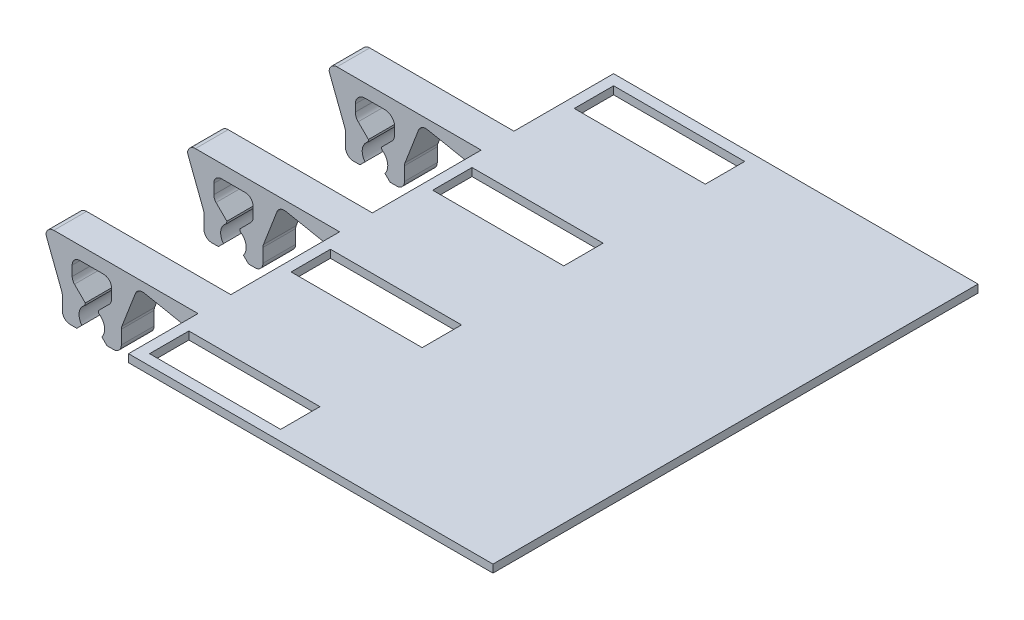
SolidWorks part; units mm, degrees
ref_plane "Front Plane" through (0, 0, 0) normal (0, 0, 1) x (1, 0, 0)
ref_plane "Top Plane" through (0, 0, 0) normal (0, 1, 0) x (1, 0, 0)
ref_plane "Right Plane" through (0, 0, 0) normal (1, 0, 0) x (0, 0, -1)
sketch "Sketch1" plane through (0, 0, 0) normal (0, 1, 0) x (1, 0, 0)
  line L1 (-27.8, -37) -> (27.8, -37)
  line L2 (-27.8, -37) -> (-27.8, 37)
  line L3 (-27.8, 37) -> (27.8, 37)
  line L4 (27.8, -37) -> (27.8, 37)
  line L5 (-27.8, -37) -> (27.8, 37) construction
  line L6 (-27.8, 37) -> (27.8, -37) construction
  point P0 (0, 0)
  dimension "D1" = 55.6
  dimension "D2" = 74
extrude "plate" add sketch "Sketch1" along normal blind 1.2
sketch "Sketch5" plane through (0, 1.2, 0) normal (0, 1, 0) x (1, 0, 0)
  line L1 (-26.2, 29.4) -> (-6.2, 29.4)
  line L2 (-26.2, 29.4) -> (-26.2, 35.4)
  line L3 (-26.2, 35.4) -> (-6.2, 35.4)
  line L4 (-6.2, 29.4) -> (-6.2, 35.4)
  line L5 (-27.8, 37) -> (-27.8, -37) construction
  line L7 (27.8, 37) -> (-27.8, 37) construction
  dimension "D1" = 20
  dimension "D2" = 6
  dimension "D3" = 1.6
  dimension "D4" = 1.6
extrude "air window" cut sketch "Sketch5" against normal blind 1.6
pattern_linear "windows" count 4 spacing 21.6 along (0, 0, 1) of "air window"
ref_plane "slot end 1" through (0, 0, -29.4) normal (0, 0, -1) x (-1, 0, 0)
ref_plane "slot start 2" through (0, 0, -13.8) normal (0, 0, 1) x (1, 0, 0)
ref_plane "Plane3" through (0, 0, -16.8) normal (0, 0, 1) x (1, 0, 0)
ref_plane "rod plane" through (0, -8, 0) normal (0, -1, 0) x (-1, 0, 0)
ref_axis "front rod" through (-44, -8, -44.0643) along (0, 0, -1)
ref_axis "back rod" through (14, -8, -40.7) along (0, 0, 1)
sketch "Sketch9" plane through (0, -8, 0) normal (0, -1, 0) x (-1, 0, 0)
  line L0 (44, 0) -> (-14, 0) construction
  line L1 (44, 44.0643) -> (44, 157.3237) construction
  line L2 (-14, 40.7) -> (-14, -40.7) construction
  point P9 (15, 0)
ref_plane "mid rods" through (-15, -8, 0) normal (1, 0, 0) x (0, 0, -1)
sketch "Sketch6" plane through (0, 0, -16.8) normal (0, 0, 1) x (1, 0, 0)
  line L5 (-37, 0) -> (-39.5, -6.5)
  line L7 (9.5, -6.5) -> (-39.5, -6.5) construction
  line L10 (14, -1.4409) -> (14, 65.3362) construction
  line L11 (14, -10) -> (14, 0) construction
  line L12 (-27.8, 0) -> (27.8, 0) construction
  line L13 (-48.5, -10) -> (-39.5, -10)
  line L14 (-44, -10.0897) -> (-44, 1.2) construction
  line L16 (-44, -94.8555) -> (-44, -30.3764) construction
  line L17 (7, 0) -> (21, 0)
  line L19 (-51, 1.2) -> (-27.8, 1.2)
  line L23 (-27.8, 1.2) -> (-18.6, 1.2)
  line L24 (-18.6, 1.2) -> (-18.6, 0)
  line L25 (-18.6, 0) -> (-27.8, -1.8)
  line L26 (-27.8, -1.8) -> (-37, 0)
  line L27 (-27.8, -1.8) -> (-27.8, 1.2) construction
  line L28 (-6.2, 0) -> (-26.2, 0) construction
  line L29 (-39.5, -6.5) -> (-39.5, -10)
  line L30 (-48.5, -6.5) -> (-48.5, -10)
  line L31 (-51, 0) -> (-48.5, -6.5)
  line L32 (-51, 1.2) -> (-51, 0)
  line L34 (21, 0) -> (18.5, -6.5)
  line L35 (18.5, -6.5) -> (18.5, -10)
  line L36 (9.5, -6.5) -> (9.5, -10)
  line L37 (18.5, -10) -> (9.5, -10)
  line L38 (7, 0) -> (9.5, -6.5)
  line L40 (-26.2, 1.2) -> (-6.2, 1.2) construction
  line L41 (-27.8, 1.2) -> (-27.8, 0) construction
  point P9 (14, -10)
  point P23 (-44, -4.4448)
  dimension "D2" = 3
  dimension "D3" = 10
  dimension "D4" = 9
  dimension "D5" = 3.5
  dimension "D6" = 2.5
extrude "clips" add sketch "Sketch6" against normal blind 5
sketch "Sketch7" plane through (0, 0, -16.8) normal (0, 0, 1) x (1, 0, 0)
  line L0 (-45.5, -10) -> (-42.5, -10)
  line L1 (-48.5, -10) -> (-39.5, -10) construction
  line L2 (-45.5, -10) -> (-45, -6)
  line L3 (-45, -6) -> (-47, -4)
  line L6 (-41, -0.8) -> (-41, -4)
  line L7 (-41, -4) -> (-43, -6)
  line L8 (-43, -6) -> (-42.5, -10)
  line L9 (-44.9448, 0) -> (24.1674, 0) construction
  line L10 (14, 0) -> (14, -10) construction
  line L27 (11, -4) -> (17, -4) construction
  line L28 (-41, -4) -> (-47, -4) construction
  line L29 (-44, 0) -> (-44, -10) construction
  line L30 (13, -6) -> (12.5, -10)
  line L31 (11, -4) -> (13, -6)
  line L32 (11, 0) -> (11, -4)
  line L33 (17, 0) -> (11, 0)
  line L34 (17, -4) -> (17, 0)
  line L35 (15, -6) -> (17, -4)
  line L36 (15.5, -10) -> (15, -6)
  line L37 (15.5, -10) -> (12.5, -10)
  line L39 (21, 0) -> (7, 0) construction
  line L40 (-45, -6) -> (-43, -6) construction
  line L41 (-41, -0.8) -> (-47, -0.8)
  line L42 (-47, -0.8) -> (-47, -4)
  line L43 (-27.8, 1.2) -> (-51, 1.2) construction
  line L44 (21, 0) -> (7, 0) construction
  point P4 (-44, -10)
  point P8 (-44, -4)
  dimension "D1" = 3
  dimension "D2" = 6
  dimension "D3" = 4
  dimension "D4" = 2
  dimension "D5" = 45
  dimension "D6" = 2
extrude "clip cut1" cut sketch "Sketch7" against normal through all
sketch "Sketch8" plane through (0, 0, -16.8) normal (0, 0, 1) x (1, 0, 0)
  line L0 (-45.25, -8) -> (-42.75, -8) construction
  line L1 (-45, -6) -> (-45.5, -10) construction
  line L2 (-42.5, -10) -> (-43, -6) construction
  circle A0 centre (-44, -8) radius 1.95
  circle A1 centre (14, -8) radius 1.95
  dimension "D1" = 3.9
extrude "clip cut2" cut sketch "Sketch8" against normal through all
fillet "Fillet1" radius 1.2 17 edges at (-48.5, -10, -19.3) (-51, 1.2, -19.3) (-51, 0, -19.3) (-48.5, -6.5, -19.3) (-41, -4, -19.3) (-39.5, -10, -19.3) (-39.5, -6.5, -19.3) (9.5, -10, -19.3) (18.5, -10, -19.3) (18.5, -6.5, -19.3) (9.5, -6.5, -19.3) (7, 0, -19.3) (21, 0, -19.3) (-37, 0, -19.3) (-47, -4, -19.3) (-41, -0.8, -19.3) (-47, -0.8, -19.3)
chamfer "Chamfer1" distance 0.8 angle 45 4 edges at (-45.5, -10, -19.3) (-42.5, -10, -19.3) (12.5, -10, -19.3) (15.5, -10, -19.3) first distance on face at (-46.4, -10, -19.3) first distance on face at (-41.6, -10, -19.3) first distance on face at (12.5413, -9.6696, -19.3) first distance on face at (16.4, -10, -19.3)
pattern_linear "LPattern2" count 3 spacing 21.6 along (0, 0, 1) of "clips", "clip cut1", "clip cut2", "Fillet1", "Chamfer1"
fillet "Fillet3" radius 1.5 16 edges at (11, 0, -19.3) (17, 0, -19.3) (17, -4, -19.3) (11, -4, -19.3) (-41, -4, -19.3) (-47, -0.8, -19.3) (-41, -0.8, -19.3) (-47, -4, -19.3) (11, -4, 23.9) (11, -4, 2.3) (17, -4, 2.3) (17, -4, 23.9) (17, 0, 23.9) (17, 0, 2.3) (11, 0, 23.9) (11, 0, 2.3)
